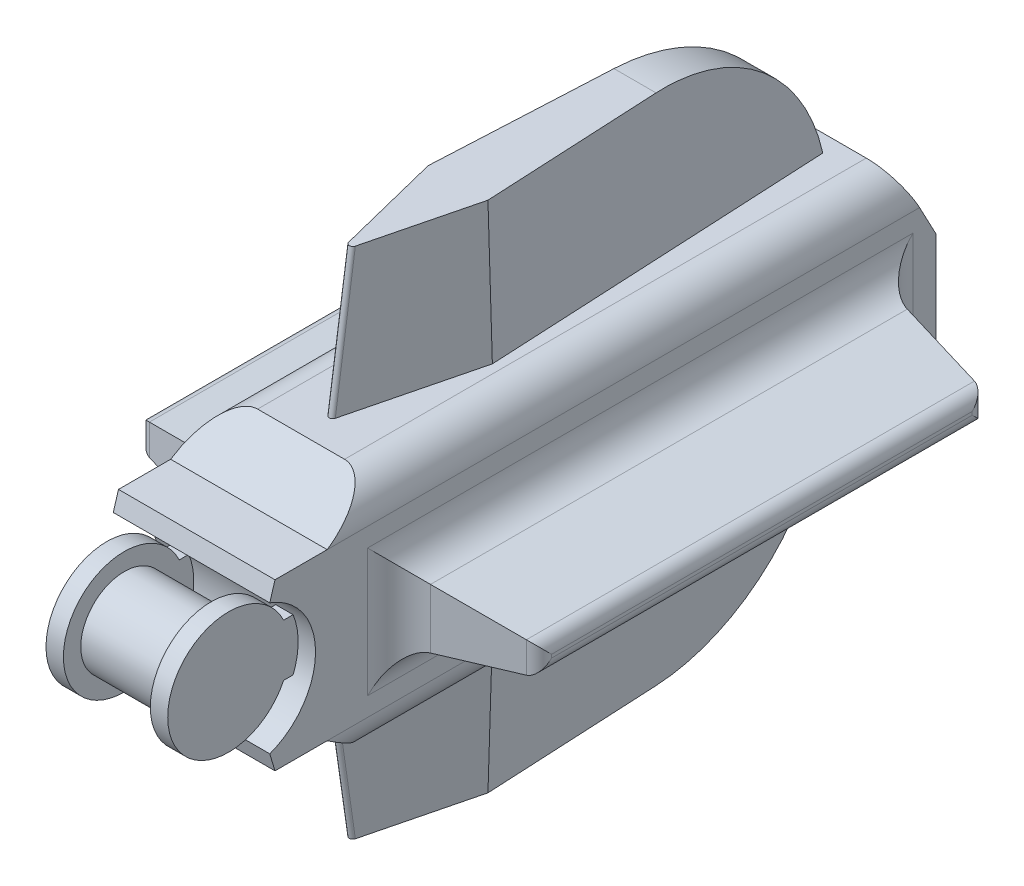
SolidWorks part; units mm, degrees
ref_plane "Front Plane" through (0, 0, 0) normal (0, 0, 1) x (1, 0, 0)
ref_plane "Top Plane" through (0, 0, 0) normal (0, 1, 0) x (1, 0, 0)
ref_plane "Right Plane" through (0, 0, 0) normal (1, 0, 0) x (0, 0, -1)
sketch "Sketch1" plane through (0, 0, 0) normal (1, 0, 0) x (0, 0, -1)
  circle A0 centre (0, 0) radius 3.175
  dimension "D1" = 6.35
extrude "Boss-Extrude1" add sketch "Sketch1" along normal mid plane 6.35
sketch "Sketch2" plane through (3.175, 0, 0) normal (1, 0, 0) x (0, 0, -1)
  circle A0 centre (0, 0) radius 4.445
  dimension "D1" = 8.89
extrude "Boss-Extrude2" add sketch "Sketch2" along normal blind 1.27
mirror "Mirror1" about plane through (0, 0, 0) normal (1, 0, 0) of "Boss-Extrude2"
sketch "Sketch3" plane through (4.445, 0, 0) normal (1, 0, 0) x (0, 0, -1)
  line L1 (0, 1.905) -> (6.35, 1.905)
  line L2 (0, 1.905) -> (0, -1.905)
  line L3 (0, -1.905) -> (6.35, -1.905)
  line L4 (6.35, 1.905) -> (6.35, -1.905)
  point P4 (0, 0)
  dimension "D1" = 3.81
  dimension "D2" = 6.35
extrude "Boss-Extrude3" add sketch "Sketch3" against normal blind 1.27
mirror "Mirror2" about plane through (0, 0, 0) normal (1, 0, 0) of "Boss-Extrude3"
sketch "Sketch4" plane through (-3.175, 0, 0) normal (1, 0, 0) x (0, 0, -1)
  line L0 (1.7375, 4.7736) -> (0, 0) construction
  line L1 (0, 0) -> (5.08, 0) construction
  line L2 (1.7375, 4.7736) -> (2.1185, 6.0436)
  line L3 (2.1185, 6.0436) -> (5.9285, 6.0436)
  line L4 (0, 0) -> (1.7375, -4.7736) construction
  line L5 (5.9285, 6.0436) -> (9.7385, 8.5836)
  line L6 (9.7385, 8.5836) -> (47.8385, 8.5836)
  line L7 (47.8385, 8.5836) -> (50.3785, 3.81)
  line L8 (50.3785, 3.81) -> (50.3785, -3.81)
  line L9 (50.3785, 0) -> (5.08, 0) construction
  line L10 (47.8385, -8.5836) -> (50.3785, -3.81)
  line L11 (9.7385, -8.5836) -> (47.8385, -8.5836)
  line L12 (5.9285, -6.0436) -> (9.7385, -8.5836)
  line L13 (2.1185, -6.0436) -> (5.9285, -6.0436)
  line L14 (1.7375, -4.7736) -> (2.1185, -6.0436)
  arc A0 (1.7375, 4.7736) -> (1.7375, -4.7736) centre (0, 0) cw
  dimension "D1" = 5.08
  dimension "D2" = 140
  dimension "D3" = 1.27
  dimension "D4" = 0.381
  dimension "D5" = 3.81
  dimension "D6" = 3.81
  dimension "D7" = 2.54
  dimension "D8" = 38.1
  dimension "D9" = 7.62
  dimension "D10" = 2.54
extrude "Boss-Extrude4" add sketch "Sketch4" against normal blind 2.54 and the other way blind 8.89
sketch "Sketch5" plane through (0, 0, -50.3785) normal (0, 0, -1) x (-1, 0, 0)
  circle A0 centre (0, 0) radius 3.175
  dimension "D1" = 6.35
extrude "Cut-Extrude1" cut sketch "Sketch5" against normal blind 12.7
fillet "Fillet1" radius 2.54 4 edges at (5.715, -8.5836, -28.7885) (-5.715, -8.5836, -28.7885) (-5.715, 8.5836, -28.7885) (5.715, 8.5836, -28.7885)
sketch "Sketch6" plane through (5.715, 0, 0) normal (1, 0, 0) x (0, 0, -1)
  line L0 (50.3785, -3.81) -> (50.3785, 3.81) construction
  line L1 (11.0085, 2.54) -> (46.5685, 2.54)
  line L2 (11.0085, 2.54) -> (11.0085, -2.54)
  line L3 (11.0085, -2.54) -> (46.5685, -2.54)
  line L4 (46.5685, 2.54) -> (46.5685, -2.54)
  point P4 (11.0085, 0)
  point P6 (50.3785, 0)
  dimension "D1" = 3.81
  dimension "D2" = 5.08
  dimension "D3" = 35.56
extrude "Boss-Extrude5" add sketch "Sketch6" along normal blind 8.89 draft 10
mirror "Mirror3" about plane through (0, 0, 0) normal (1, 0, 0) of "Boss-Extrude5"
fillet "Fillet2" radius 1.016 8 edges at (-14.605, -0.9725, -28.7885) (-14.605, 0, -45.0009) (-14.605, 0.9725, -28.7885) (-14.605, 0, -12.576) (14.605, 0.9725, -28.7885) (14.605, 0, -45.0009) (14.605, -0.9725, -28.7885) (14.605, 0, -12.576)
fillet "Fillet3" radius 2.54 8 edges at (5.715, -2.54, -28.7885) (5.715, 0, -11.0085) (5.715, 0, -46.5685) (5.715, 2.54, -28.7885) (-5.715, 0, -11.0085) (-5.715, 0, -46.5685) (-5.715, -2.54, -28.7885) (-5.715, 2.54, -28.7885)
sketch "Sketch7" plane through (0, 8.5836, 0) normal (0, 1, 0) x (1, 0, 0)
  line L0 (0, 9.7385) -> (0, 47.8385) construction
  line L1 (3.175, 9.7385) -> (-3.175, 9.7385) construction
  line L2 (3.175, 47.8385) -> (-3.175, 47.8385) construction
  line L3 (-1.27, 46.5685) -> (1.27, 46.5685)
  line L4 (1.27, 46.5685) -> (2.54, 21.1685)
  line L5 (2.54, 21.1685) -> (0, 11.0085)
  line L6 (0, 11.0085) -> (-2.54, 21.1685)
  line L7 (-2.54, 21.1685) -> (-1.27, 46.5685)
  point P8 (0, 46.5685)
  dimension "D1" = 2.54
  dimension "D2" = 1.27
  dimension "D3" = 1.27
  dimension "D4" = 2.54
  dimension "D5" = 25.4
extrude "Boss-Extrude6" add sketch "Sketch7" along normal blind 10.16 draft 2
mirror "Mirror4" about plane through (0, 0, 0) normal (0, 1, 0) of "Boss-Extrude6"
fillet "Fillet4" radius 0.254 2 edges at (0, -13.6636, -11.7399) (0, 13.6636, -11.7399)
fillet "Fillet5" radius 12.7 2 edges at (0, -18.7436, -46.2137) (0, 18.7436, -46.2137)
